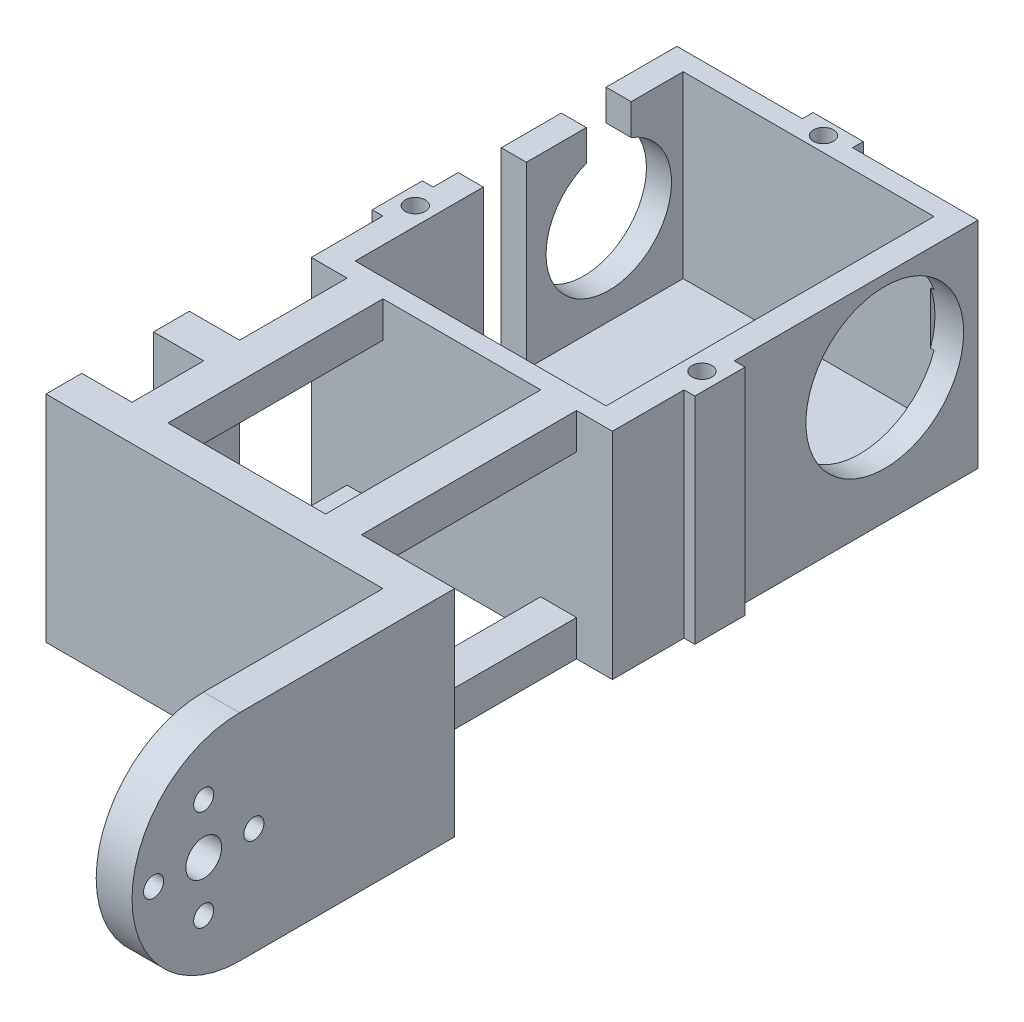
SolidWorks part; units mm, degrees
ref_plane "Front Plane" through (0, 0, 0) normal (0, 0, 1) x (1, 0, 0)
ref_plane "Top Plane" through (0, 0, 0) normal (0, 1, 0) x (1, 0, 0)
ref_plane "Right Plane" through (0, 0, 0) normal (1, 0, 0) x (0, 0, -1)
sketch "Sketch1" plane through (0, 0, 0) normal (0, 1, 0) x (1, 0, 0)
  line L1 (-21, 25.5) -> (21, 25.5)
  line L2 (-21, 25.5) -> (-21, -25.5)
  line L3 (-21, -25.5) -> (21, -25.5)
  line L4 (21, 25.5) -> (21, -25.5)
  line L5 (-11, -25.5) -> (-16, -25.5)
  line L6 (-11, -25.5) -> (-11, -55.5)
  line L7 (-11, -55.5) -> (-16, -55.5)
  line L8 (-16, -25.5) -> (-16, -55.5)
  line L9 (16, -25.5) -> (11, -25.5)
  line L10 (16, -25.5) -> (16, -55.5)
  line L11 (16, -55.5) -> (11, -55.5)
  line L12 (11, -25.5) -> (11, -55.5)
  line L13 (-16, -55.5) -> (29, -55.5)
  line L14 (-16, -55.5) -> (-16, -60.5)
  line L15 (-16, -60.5) -> (29, -60.5)
  line L16 (29, -55.5) -> (29, -60.5)
  line L21 (29, -60.5) -> (24, -60.5)
  line L22 (29, -60.5) -> (29, -100.5)
  line L23 (29, -100.5) -> (24, -100.5)
  line L24 (24, -60.5) -> (24, -100.5)
  line L25 (-16, -45.5) -> (-23, -45.5)
  line L26 (-16, -45.5) -> (-16, -40.5)
  line L27 (-16, -40.5) -> (-23, -40.5)
  line L28 (-23, -45.5) -> (-23, -40.5)
  line L29 (-16, -55.5) -> (-23, -55.5)
  line L30 (-16, -55.5) -> (-16, -60.5)
  line L31 (-16, -60.5) -> (-23, -60.5)
  line L32 (-23, -55.5) -> (-23, -60.5)
  point P4 (-21, 0)
  point P6 (0, 25.5)
  dimension "D1" = 42
  dimension "D2" = 51
  dimension "D3" = 5
  dimension "D4" = 30
  dimension "D5" = 5
  dimension "D6" = 5
  dimension "D7" = 45
  dimension "D8" = 7
  dimension "D9" = 40
  dimension "D10" = 10
extrude "Boss-Extrude1" add sketch "Sketch1" along normal blind 5 contours L4 L1 L2 L3 region at (0, 0, 0)
sketch "Sketch3" plane through (0, 5, 0) normal (0, 1, 0) x (1, 0, 0)
  line L1 (-17.5, 22.875) -> (17.5, 22.875)
  line L2 (-17.5, 22.875) -> (-17.5, -22.875)
  line L3 (-17.5, -22.875) -> (17.5, -22.875)
  line L4 (17.5, 22.875) -> (17.5, -22.875)
  line L5 (-21, 25.5) -> (21, 25.5)
  line L6 (-21, 25.5) -> (-21, -25.5)
  line L7 (-21, -25.5) -> (21, -25.5)
  line L8 (21, 25.5) -> (21, -25.5)
  point P4 (-17.5, 0)
  point P6 (0, 22.875)
  dimension "D1" = 35
  dimension "D2" = 45.75
extrude "Boss-Extrude3" add sketch "Sketch3" along normal blind 25
sketch "Sketch4" plane through (-21, 0, 0) normal (-1, 0, 0) x (0, 0, 1)
  line L1 (-25.5, 30) -> (25.5, 30) construction
  line L2 (0, 30) -> (0, 0) construction
  circle A0 centre (-12.5, 17.5) radius 8.75
  dimension "D2" = 17.5
  dimension "D1" = 12.5
  dimension "D3" = 12.5
extrude "Cut-Extrude2" cut sketch "Sketch4" against normal blind 5
sketch "Sketch6" plane through (-17.5, 0, 0) normal (1, 0, 0) x (0, 0, -1)
  line L0 (-25.5, 30) -> (25.5, 30) construction
  line L2 (0, 30) -> (0, 0) construction
  line L4 (9.375, 17.5) -> (9.375, 30)
  line L5 (9.375, 30) -> (15.625, 30)
  line L6 (15.625, 17.5) -> (15.625, 30)
  line L7 (25.5, 0) -> (-25.5, 0) construction
  arc A0 (9.375, 17.5) -> (15.625, 17.5) centre (12.5, 17.5) ccw
  point P11 (12.5, 30)
  dimension "D1" = 6.25
  dimension "D2" = 12.5
  dimension "D3" = 12.5
extrude "Cut-Extrude3" cut sketch "Sketch6" against normal blind 4
sketch "Sketch7" plane through (-21, 0, 0) normal (-1, 0, 0) x (0, 0, 1)
  line L0 (-9.375, 30) -> (25.5, 30) construction
  line L1 (-1, 30) -> (5, 30)
  line L2 (-1, 30) -> (-1, 5)
  line L3 (-1, 5) -> (5, 5)
  line L4 (5, 30) -> (5, 5)
  line L6 (25.5, 30) -> (25.5, 0) construction
  line L7 (-25.5, 0) -> (25.5, 0) construction
  dimension "D1" = 20.5
  dimension "D2" = 5
  dimension "D3" = 6
extrude "Cut-Extrude4" cut sketch "Sketch7" against normal blind 4
sketch "Sketch9" plane through (21, 0, 0) normal (1, 0, 0) x (0, 0, -1)
  line L0 (25.5, 30) -> (25.5, 0) construction
  line L1 (-25.5, 30) -> (25.5, 30) construction
  circle A0 centre (12.5, 17.5) radius 11
  dimension "D2" = 22
  dimension "D1" = 13
  dimension "D3" = 12.5
extrude "Cut-Extrude5" cut sketch "Sketch9" against normal blind 4
sketch "Sketch16" plane through (-21, 0, 0) normal (-1, 0, 0) x (0, 0, 1)
  line L0 (5, 30) -> (25.5, 30) construction
  line L1 (15.5, 30) -> (8.5, 30)
  line L2 (15.5, 30) -> (15.5, 0)
  line L3 (15.5, 0) -> (8.5, 0)
  line L4 (8.5, 30) -> (8.5, 0)
  line L5 (-25.5, 0) -> (25.5, 0) construction
  line L6 (25.5, 30) -> (25.5, 0) construction
  dimension "D1" = 10
  dimension "D2" = 7
extrude "Boss-Extrude5" add sketch "Sketch16" along normal blind 1.5
sketch "Sketch17" plane through (21, 0, 0) normal (1, 0, 0) x (0, 0, -1)
  line L0 (-25.5, 30) -> (25.5, 30) construction
  line L1 (-15.5, 30) -> (-8.5, 30)
  line L2 (-15.5, 30) -> (-15.5, 0)
  line L3 (-15.5, 0) -> (-8.5, 0)
  line L4 (-8.5, 30) -> (-8.5, 0)
  line L5 (25.5, 0) -> (-25.5, 0) construction
  line L6 (-25.5, 30) -> (-25.5, 0) construction
  dimension "D1" = 10
  dimension "D2" = 7
extrude "Boss-Extrude6" add sketch "Sketch17" along normal blind 1.5
sketch "Sketch19" plane through (0, 0, -25.5) normal (0, 0, -1) x (-1, 0, 0)
  line L0 (-21, 30) -> (21, 30) construction
  line L1 (3.5, 30) -> (-3.5, 30)
  line L2 (3.5, 30) -> (3.5, 0)
  line L3 (3.5, 0) -> (-3.5, 0)
  line L4 (-3.5, 30) -> (-3.5, 0)
  line L5 (21, 0) -> (-21, 0) construction
  point P8 (0, 0)
  point P9 (0, 30)
  dimension "D1" = 7
extrude "Boss-Extrude7" add sketch "Sketch19" along normal blind 1.5
sketch "Sketch18" plane through (0, 30, 0) normal (0, 1, 0) x (1, 0, 0)
  line L0 (-22.5, -15.5) -> (-22.5, -8.5) construction
  line L1 (0, -19.5533) -> (0, 11.7982) construction
  line L2 (-3.5, 27) -> (3.5, 27) construction
  line L3 (-22.5, -12) -> (-17.5, -12) construction
  line L4 (-17.5, -5) -> (-17.5, -22.875) construction
  line L5 (0, 27) -> (0, 22.875) construction
  line L6 (17.5, 22.875) -> (-17.5, 22.875) construction
  circle A0 centre (-20, -12) radius 1.4
  circle A1 centre (20, -12) radius 1.4
  circle A2 centre (0, 24.9375) radius 1.4
  point P5 (-22.5, -12)
  point P17 (0, 27)
  point P21 (-20, -12)
  point P26 (0, 24.9375)
  dimension "D1" = 2.8
extrude "Cut-Extrude7" cut sketch "Sketch18" against normal blind 6
extrude "Boss-Extrude8" add sketch "Sketch1<3>" along normal blind 30 contours L3 L8 L7 L6 | L3 L12 L11 L10 | L16 L13 L11 L7 L14 L15 | L15 L24 L23 L22 | L15 | L26 L25 L28 L27 | L30 L29 L32 L31 region at (-13.5, 0, 40.5) region at (13.5, 0, 40.5) region at (6.5, 0, 58) region at (26.5, 0, 80.5)
sketch "Sketch1<3>" plane through (0, 0, 0) normal (0, 1, 0) x (1, 0, 0) same geometry as "Sketch1"
sketch "Sketch24" plane through (-16, 0, 0) normal (-1, 0, 0) x (0, 0, 1)
  line L0 (25.5, 30) -> (25.5, 0) construction
  line L1 (25.5, 25) -> (55.5, 25)
  line L2 (25.5, 25) -> (25.5, 5)
  line L3 (25.5, 5) -> (55.5, 5)
  line L4 (55.5, 25) -> (55.5, 5)
  line L5 (55.5, 30) -> (55.5, 0) construction
  point P8 (25.5, 15)
  point P9 (25.5, 15)
  dimension "D1" = 20
extrude "Cut-Extrude8" cut sketch "Sketch24" against normal blind 32
sketch "Sketch28" plane through (24, 0, 0) normal (-1, 0, 0) x (0, 0, 1)
  line L0 (83.5, 15) -> (90.5, 15) construction
  line L1 (90.5, 15) -> (90.5, 22) construction
  line L2 (100.5, 30) -> (100.5, 0) construction
  circle A0 centre (90.5, 15) radius 2.5
  circle A1 centre (90.5, 22) radius 1.4
  circle A2 centre (83.5, 15) radius 1.4
  circle A3 centre (90.5, 8) radius 1.4
  circle A4 centre (97.5, 15) radius 1.4
  point P12 (100.5, 15)
  dimension "D2" = 2.8
  dimension "D3" = 5
  dimension "D1" = 7
  dimension "D4" = 10
sketch "Sketch29" plane through (-23, 0, 0) normal (-1, 0, 0) x (0, 0, 1)
  line L0 (55.5, 30) -> (60.5, 30) construction
  line L1 (40.5, 15) -> (60.5, 15) construction
  line L2 (40.5, 30) -> (40.5, 0) construction
  line L3 (60.5, 30) -> (60.5, 0) construction
  line L4 (50.5, 30) -> (50.5, 0) construction
  line L5 (45.5, 30) -> (55.5, 30) construction
  line L6 (45.5, 0) -> (55.5, 0) construction
  circle A0 centre (58, 25) radius 1.4
  circle A1 centre (43, 25) radius 1.4
  circle A2 centre (58, 5) radius 1.4
  circle A3 centre (43, 5) radius 1.4
  point P4 (58, 30)
  dimension "D2" = 2.8
  dimension "D1" = 5
extrude "Cut-Extrude9" cut sketch "Sketch29" against normal blind 6
sketch "Sketch30" plane through (29, 0, 0) normal (1, 0, 0) x (0, 0, -1)
  line L0 (-100.5, 30) -> (-100.5, 0) construction
  line L1 (-55.5, 30) -> (-100.5, 30) construction
  line L2 (-85.5, 30) -> (-100.5, 30)
  line L3 (-100.5, 30) -> (-100.5, 15)
  line L4 (-100.5, 0) -> (-85.5, 0)
  line L5 (-85.5, 30) -> (-85.5, 0) construction
  line L6 (-100.5, 0) -> (-100.5, 15)
  line L7 (-100.5, 15) -> (-85.5, 15) construction
  arc A0 (-100.5, 15) -> (-85.5, 0) centre (-85.5, 15) ccw
  arc A1 (-85.5, 30) -> (-100.5, 15) centre (-85.5, 15) ccw
  point P4 (-100.5, 15)
extrude "Cut-Extrude10" cut sketch "Sketch30" against normal blind 6 contours A0 L4 L6 | L3 L2 A1
extrude "Cut-Extrude11" cut sketch "Sketch28" against normal blind 6
